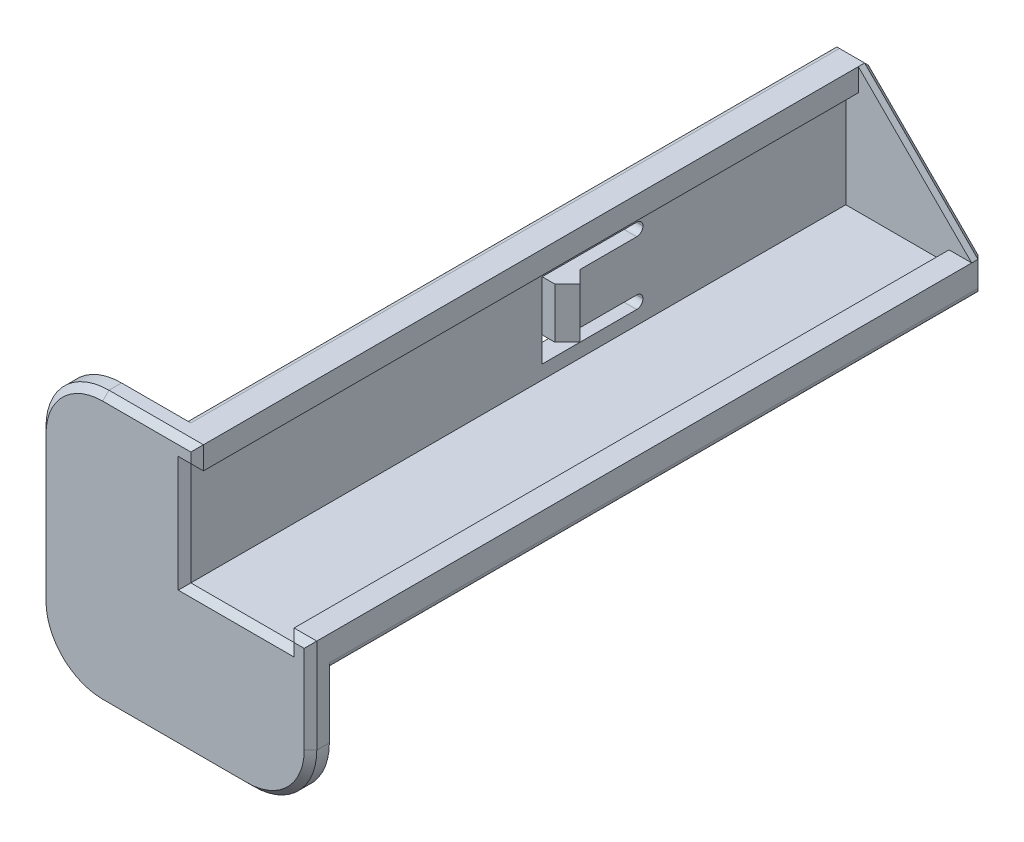
SolidWorks part; units mm, degrees
material "PE High Density"
ref_plane "Front Plane" through (0, 0, 0) normal (0, 0, 1) x (1, 0, 0)
ref_plane "Top Plane" through (0, 0, 0) normal (0, 1, 0) x (1, 0, 0)
ref_plane "Right Plane" through (0, 0, 0) normal (1, 0, 0) x (0, 0, -1)
sketch "Sketch1" plane through (0, 0, 0) normal (0, 0, 1) x (1, 0, 0)
  line L1 (-121.6, -26.1) -> (-124.1, -26.1)
  line L2 (-121.6, -26.1) -> (-121.6, -27.9)
  line L3 (-121.6, -27.9) -> (-122.6, -27.9)
  line L6 (-124.1, -26.1) -> (-124.1, -37.6)
  line L8 (-122.6, -27.9) -> (-122.6, -36.1)
  line L9 (-124.1, -37.6) -> (-112.6, -37.6)
  line L11 (-122.6, -36.1) -> (-114.4, -36.1)
  line L14 (-112.6, -37.6) -> (-112.6, -35.1)
  line L15 (-112.6, -35.1) -> (-114.4, -35.1)
  line L16 (-114.4, -36.1) -> (-114.4, -35.1)
  dimension "D9" = 1.5
  dimension "D10" = 1.5
extrude "Boss-Extrude1" add sketch "Sketch1" against normal blind 52.5
sketch "Sketch2" plane through (0, 0, 0) normal (0, 0, 1) x (1, 0, 0)
  line L1 (-124.1, -26.1) -> (-134.1, -26.1)
  line L2 (-124.1, -26.1) -> (-124.1, -37.6)
  line L3 (-112.6, -47.6) -> (-134.1, -47.6)
  line L4 (-134.1, -26.1) -> (-134.1, -47.6)
  line L5 (-112.6, -37.6) -> (-124.1, -37.6)
  line L6 (-112.6, -37.6) -> (-112.6, -47.6)
  dimension "D1" = 10
  dimension "D2" = 10
extrude "Boss-Extrude2" add sketch "Sketch2" against normal blind 1.5
sketch "Sketch4" plane through (-122.6, 0, 0) normal (1, 0, 0) x (0, 0, -1)
  line L1 (52.5, -36.1) -> (52.5, -27.9) construction
  line L3 (52.5, -32) -> (0, -32) construction
  line L5 (0, -36.1) -> (0, -27.9) construction
  line L6 (36.4, -30) -> (36.4, -29)
  line L7 (28.4, -35) -> (36.4, -35)
  line L8 (28.4, -35) -> (28.4, -29)
  line L9 (28.4, -29) -> (36.4, -29)
  line L10 (36.4, -35) -> (36.4, -34)
  line L11 (29.4, -34) -> (36.4, -34)
  line L12 (29.4, -34) -> (29.4, -30)
  line L13 (29.4, -30) -> (36.4, -30)
  dimension "D1" = 28.4
  dimension "D2" = 1
  dimension "D3" = 1
  dimension "D4" = 1
  dimension "D5" = 4
  dimension "D6" = 7
extrude "Cut-Extrude1" cut sketch "Sketch4" against normal up to next
sketch "Sketch5" plane through (-122.6, 0, 0) normal (1, 0, 0) x (0, 0, -1)
  line L0 (29.4, -32) -> (10.5494, -32) construction
  line L1 (29.4, -34) -> (29.4, -30) construction
  line L3 (29.4, -34) -> (31.4, -34)
  line L4 (29.4, -34) -> (29.4, -30)
  line L5 (29.4, -30) -> (31.4, -30)
  line L6 (31.4, -34) -> (31.4, -30)
  dimension "D1" = 4
  dimension "D2" = 2
  dimension "D3" = 0
extrude "Boss-Extrude3" add sketch "Sketch5" along normal blind 1
fillet "Fillet1" radius 5 3 edges at (-134.1, -26.1, -0.75) (-134.1, -47.6, -0.75) (-112.6, -47.6, -0.75)
sketch "Sketch6" plane through (0, 0, -52.5) normal (0, 0, -1) x (-1, 0, 0)
  line L0 (112.6, -35.1) -> (112.6, -37.6)
  line L1 (112.6, -37.6) -> (124.1, -37.6)
  line L2 (124.1, -37.6) -> (124.1, -26.1)
  line L3 (121.6, -26.1) -> (124.1, -26.1) construction
  line L4 (124.1, -26.1) -> (124.1, -37.6) construction
  line L5 (124.1, -26.1) -> (121.6, -26.1)
  line L6 (121.6, -26.1) -> (112.6, -35.1)
extrude "Boss-Extrude4" add sketch "Sketch6" along normal blind 1
chamfer "Chamfer3" distance 0.5 angle 45 18 edges at (-113.5, -35.1, 0) (-121.6, -27, 0) (-118.5, -36.1, 0) (-122.6, -32, 0) (-125.35, -26.1, 0) (-132.6355, -27.5645, 0) (-134.1, -36.85, 0) (-132.6355, -46.1355, 0) (-123.35, -47.6, 0) (-114.0645, -46.1355, 0) (-112.6, -38.85, 0) (-114.4, -35.6, 0) (-122.1, -27.9, 0) (-122.85, -26.1, -53.5) (-124.1, -31.85, -53.5) (-118.35, -37.6, -53.5) (-112.6, -36.35, -53.5) (-117.1, -30.6, -53.5)
chamfer "Chamfer4" distance 1 angle 45 2 edges at (-121.6, -32, -31.4) (-121.6, -32, -29.4)
fillet "Fillet3" radius 0.5 4 edges at (-123.35, -29, -36.4) (-123.35, -30, -36.4) (-123.35, -34, -36.4) (-123.35, -35, -36.4)
fillet "Fillet4" radius 0.5 3 edges at (-112.6, -37.6, -27.25) (-124.1, -26.1, -27.25) (-124.1, -37.6, -27.25)
